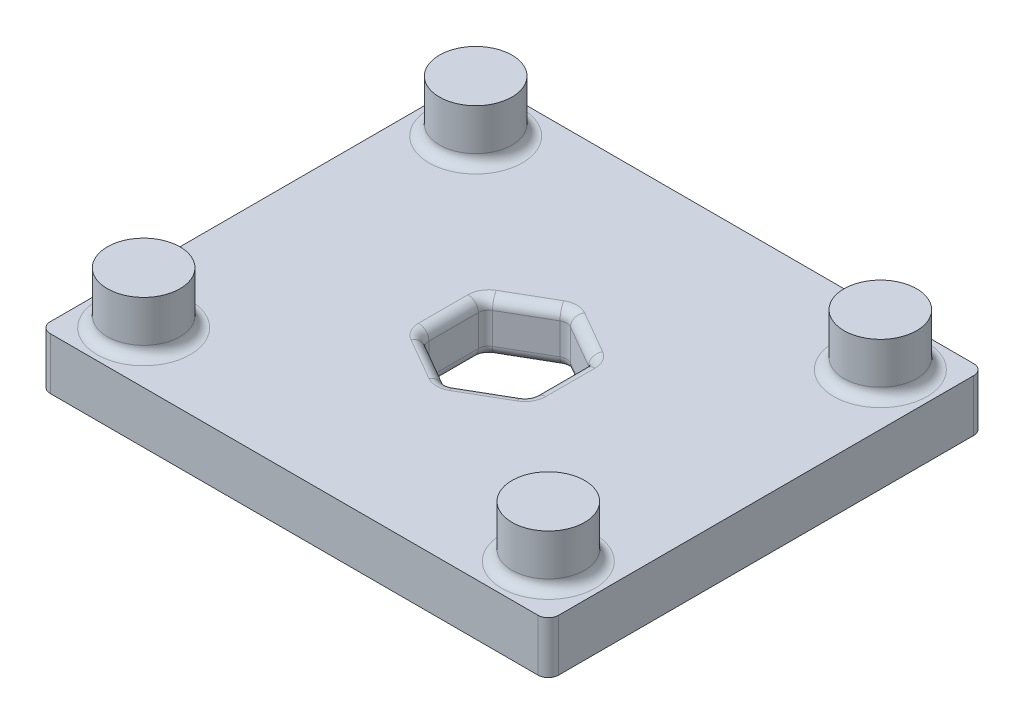
SolidWorks part; units mm, degrees
ref_plane "Front Plane" through (0, 0, 0) normal (0, 0, 1) x (1, 0, 0)
ref_plane "Top Plane" through (0, 0, 0) normal (0, 1, 0) x (1, 0, 0)
ref_plane "Right Plane" through (0, 0, 0) normal (1, 0, 0) x (0, 0, -1)
sketch "Sketch2" plane through (0, 0, 0) normal (0, 1, 0) x (1, 0, 0)
  line L4 (-24.5, -21) -> (24.5, -21)
  line L15 (24.5, -21) -> (24.5, 21)
  line L16 (24.5, 21) -> (-24.5, 21)
  line L17 (-24.5, 21) -> (-24.5, -21)
  line L18 (0, 0) -> (24.5, 0)
  line L19 (0, 0) -> (-24.5, 0)
  line L21 (-0.5, -5.9178) -> (4.625, -2.9589)
  line L22 (4.625, -2.9589) -> (4.625, 2.9589)
  line L23 (4.625, 2.9589) -> (-0.5, 5.9178)
  line L24 (-0.5, 5.9178) -> (-5.625, 2.9589)
  line L25 (-5.625, 2.9589) -> (-5.625, -2.9589)
  line L26 (-5.625, -2.9589) -> (-0.5, -5.9178)
  circle A0 centre (-0.5, 0) radius 5.125 construction
  circle A4 centre (19.5, -16) radius 5
  circle A5 centre (19.5, -16) radius 3.5
  circle A6 centre (19.5, 16) radius 5
  circle A7 centre (19.5, 16) radius 3.5
  circle A8 centre (-19.5, 16) radius 5
  circle A9 centre (-19.5, 16) radius 3.5
  circle A10 centre (-19.5, -16) radius 5
  circle A11 centre (-19.5, -16) radius 3.5
  point P3 (0, 0)
  point P27 (0, 0)
  point P28 (0, 0)
  point P31 (-0.8767, -5.9058)
  dimension "D1" = 10.25
  dimension "D3" = 10
  dimension "D4" = 7
  dimension "D5" = 21
  dimension "D2" = 49
  dimension "D6" = 25
extrude "Boss-Extrude1" add sketch "Sketch2" along normal blind 5 contours A8 A9 | A8 L16 L17 | A8 L17 L19 L21 L18 L15 A6 L16 | A6 A7 | A6 L15 L16 | A10 L4 A4 L15 L18 L23 L22 L19 L17 | A4 A5 | A4 L4 L15 | A10 L17 L4 | A10 A11 | A11 | A9 | A7 | A5 region at (-23.3832, 0, 19.8832) region at (0.0279, 0, 9.7747) region at (-22.9355, 0, 19.4355) region at (23.3832, 0, 19.8832) region at (16.0645, 0, 12.5645) region at (0.0279, 0, -9.7747) region at (-23.3832, 0, -19.8832) region at (-22.9355, 0, -19.4355) region at (23.3832, 0, -19.8832) region at (16.0645, 0, -12.5645) region at (19.5, 0, 16) region at (19.5, 0, -16) region at (-19.5, 0, -16) region at (-19.5, 0, 16)
extrude "Boss-Extrude2" add sketch "Sketch2<3>" along normal blind 10 contours A9 | A7 | A5 | A11 region at (19.5, 0, 16) region at (19.5, 0, -16) region at (-19.5, 0, -16) region at (-19.5, 0, 16)
sketch "Sketch2<3>" plane through (0, 0, 0) normal (0, 1, 0) x (1, 0, 0) same geometry as "Sketch2"
fillet "Fillet1" radius 1 4 edges at (-19.5, 5, -12.5) (19.5, 5, -12.5) (19.5, 5, 19.5) (-19.5, 5, 19.5)
fillet "Fillet2" radius 1 10 edges at (4.625, 2.5, -2.9589) (4.625, 2.5, 2.9589) (-24.5, 2.5, -21) (24.5, 2.5, -21) (24.5, 2.5, 21) (-24.5, 2.5, 21) (-0.5, 2.5, -5.9178) (-5.625, 2.5, -2.9589) (-5.625, 2.5, 2.9589) (-0.5, 2.5, 5.9178)
fillet "Fillet3" radius 1 24 edges at (2.0625, 0, -4.4384) (4.491, 0, -2.8816) (4.625, 0, 0) (4.491, 5, 2.8816) (4.491, 0, 2.8816) (4.491, 5, -2.8816) (2.0625, 5, -4.4384) (2.0625, 5, 4.4384) (4.625, 5, 0) (2.0625, 0, 4.4384) (-0.5, 5, 5.7631) (-3.0625, 5, 4.4384) (-5.491, 5, 2.8816) (-5.625, 5, 0) (-5.491, 5, -2.8816) (-3.0625, 5, -4.4384) (-0.5, 5, -5.7631) (-0.5, 0, 5.7631) (-3.0625, 0, 4.4384) (-5.491, 0, 2.8816) (-5.625, 0, 0) (-5.491, 0, -2.8816) (-3.0625, 0, -4.4384) (-0.5, 0, -5.7631)
